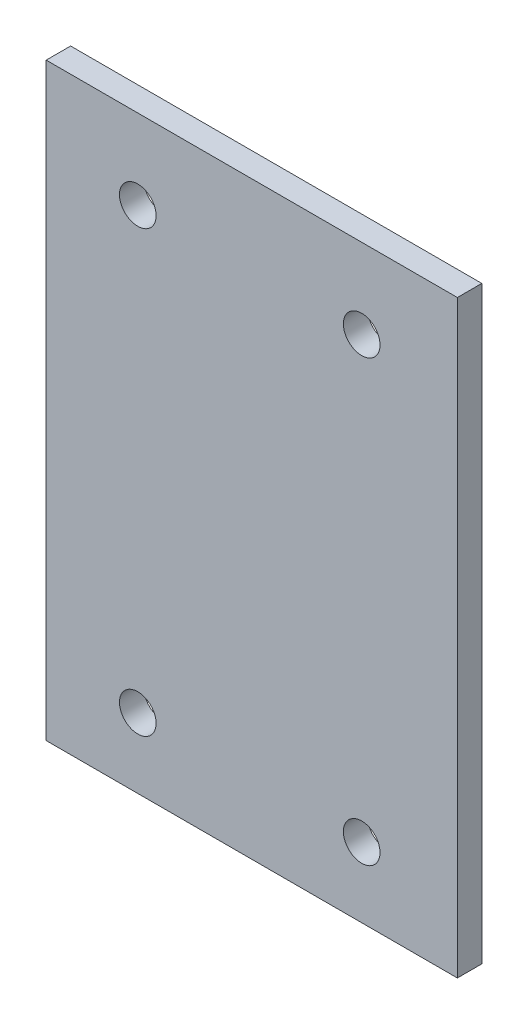
SolidWorks part; units mm, degrees
ref_plane "Front Plane" through (0, 0, 0) normal (0, 0, 1) x (1, 0, 0)
ref_plane "Top Plane" through (0, 0, 0) normal (0, 1, 0) x (1, 0, 0)
ref_plane "Right Plane" through (0, 0, 0) normal (1, 0, 0) x (0, 0, -1)
sketch "Sketch1" plane through (0, 0, 0) normal (0, 0, 1) x (1, 0, 0)
  line L1 (0, 0) -> (101, 0)
  line L2 (0, 0) -> (0, 144.7604)
  line L3 (0, 144.7604) -> (101, 144.7604)
  line L4 (101, 0) -> (101, 144.7604)
  line L5 (22.5, 125.1559) -> (77.5, 125.1559) construction
  line L6 (22.5, 125.1559) -> (22.5, 17.1559) construction
  line L7 (22.5, 17.1559) -> (77.5, 17.1559) construction
  line L8 (77.5, 125.1559) -> (77.5, 17.1559) construction
  circle A0 centre (22.5, 125.1559) radius 4.5
  circle A1 centre (77.5, 125.1559) radius 4.5
  circle A2 centre (77.5, 17.1559) radius 4.5
  circle A3 centre (22.5, 17.1559) radius 4.5
  dimension "D1" = 99
  dimension "D2" = 64
  dimension "D3" = 9
extrude "Boss-Extrude1" add sketch "Sketch1" against normal blind 6
sketch "Sketch2" plane through (0, 0, 0) normal (0, 0, 1) x (1, 0, 0)
  line L0 (-66.5, 11.1559) -> (-66.5, 156.1559) construction
  line L1 (-86.5, 156.1559) -> (-46.5, 156.1559)
  line L2 (-86.5, 156.1559) -> (-86.5, 11.1559)
  line L3 (-86.5, 11.1559) -> (-46.5, 11.1559)
  line L4 (-46.5, 156.1559) -> (-46.5, 11.1559)
  line L5 (22.5, 17.1559) -> (7.5, 17.1559)
  circle A0 centre (-66.5, 50.1559) radius 3.5
  circle A1 centre (-66.5, 60.1559) radius 3.5
  circle A2 centre (-66.5, 81.1559) radius 3.5
  circle A3 centre (-66.5, 97.1559) radius 3.5
  circle A4 centre (-75.5, 17.1559) radius 3
  circle A5 centre (-66.5, 21.1559) radius 3.5
  circle A6 centre (-57.5, 17.1559) radius 3
  circle A7 centre (-75.5, 150.1559) radius 3
  circle A8 centre (-66.5, 146.1559) radius 3.5
  circle A9 centre (-57.5, 150.1559) radius 3
  point P26 (0, 0)
  point P27 (0, 0)
  dimension "D1" = 7
  dimension "D2" = 7
  dimension "D3" = 6
  dimension "D4" = 11
  dimension "D5" = 11
  dimension "D6" = 40
  dimension "D7" = 145
  dimension "D8" = 6
  dimension "D9" = 6
  dimension "D10" = 10
  dimension "D11" = 10
  dimension "D12" = 10
  dimension "D13" = 21
  dimension "D14" = 16
  dimension "D15" = 39
  dimension "D16" = 59
  dimension "D17" = 15
  dimension "D18" = 65
